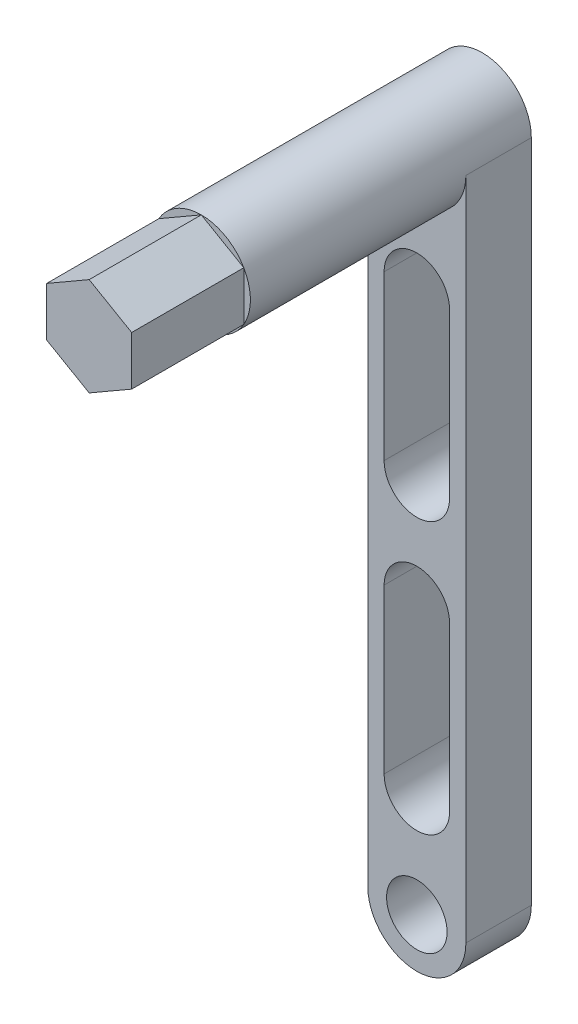
SolidWorks part; units mm, degrees
material "PEI"
ref_plane "Front Plane" through (0, 0, 0) normal (0, 0, 1) x (1, 0, 0)
ref_plane "Top Plane" through (0, 0, 0) normal (0, 1, 0) x (1, 0, 0)
ref_plane "Right Plane" through (0, 0, 0) normal (1, 0, 0) x (0, 0, -1)
sketch "Sketch1" plane through (0, 0, 0) normal (0, 0, 1) x (1, 0, 0)
  line L0 (0, -50.8) -> (0, 50.8) construction
  line L1 (-7.5, -50.8) -> (-7.5, 50.8)
  line L2 (7.5, -50.8) -> (7.5, 50.8)
  line L3 (0, -34.675) -> (0, -9.675) construction
  line L4 (-5, -34.675) -> (-5, -9.675)
  line L5 (5, -34.675) -> (5, -9.675)
  line L6 (0, 31.8) -> (0, 6.8) construction
  line L7 (5, 31.8) -> (5, 6.8)
  line L8 (-5, 31.8) -> (-5, 6.8)
  line L9 (-5, 19.3) -> (5, 19.3) construction
  line L10 (-5, -22.175) -> (5, -22.175) construction
  line L12 (0, 58.3) -> (0, 36.8) construction
  arc A0 (-7.5, -50.8) -> (7.5, -50.8) centre (0, -50.8) ccw
  arc A1 (7.5, 50.8) -> (-7.5, 50.8) centre (0, 50.8) ccw
  circle A2 centre (0, -50.8) radius 4.625
  arc A4 (-5, -34.675) -> (5, -34.675) centre (0, -34.675) ccw
  arc A5 (5, -9.675) -> (-5, -9.675) centre (0, -9.675) ccw
  arc A6 (5, 31.8) -> (-5, 31.8) centre (0, 31.8) ccw
  arc A7 (-5, 6.8) -> (5, 6.8) centre (0, 6.8) ccw
  circle A8 centre (0, 50.8) radius 7.5
  point P2 (0, 0)
  point P14 (0, -22.175)
  point P19 (0, 19.3)
  point P30 (0, -4.675)
  point P32 (0, -46.175)
  point P33 (0, -39.675)
  point P35 (0, 1.8)
  point P37 (0, 43.3)
  dimension "D3" = 9.25
  dimension "D1" = 101.6
  dimension "D2" = 15
  dimension "D4" = 10
  dimension "D5" = 6.5
  dimension "20" = 25
  dimension "D6" = 6.5
extrude "Boss-Extrude1" add sketch "Sketch1" along normal blind 10 contours A8 L1 A0 L2 A7 L8 A6 L7 A5 L5 A4 L4 A2 region at (-6.3987, 0, 0)
extrude "Boss-Extrude2" add sketch "Sketch1<4>" along normal blind 42.94 contours A1 A8 region at (0, 50.8, 0)
sketch "Sketch1<4>" plane through (0, 0, 0) normal (0, 0, 1) x (1, 0, 0) same geometry as "Sketch1"
sketch "Sketch2" plane through (0, 0, 42.94) normal (0, 0, 1) x (1, 0, 0)
  point P0 (0, 50.8)
sketch "Sketch3" plane through (0, 0, 42.94) normal (0, 0, 1) x (1, 0, 0)
  line L1 (0, 43.3) -> (6.4952, 47.05)
  line L2 (6.4952, 47.05) -> (6.4952, 54.55)
  line L3 (6.4952, 54.55) -> (0, 58.3)
  line L4 (0, 58.3) -> (-6.4952, 54.55)
  line L5 (-6.4952, 54.55) -> (-6.4952, 47.05)
  line L6 (-6.4952, 47.05) -> (0, 43.3)
  circle A0 centre (0, 50.8) radius 6.4952 construction
extrude "Boss-Extrude3" add sketch "Sketch3" along normal blind 17.14
